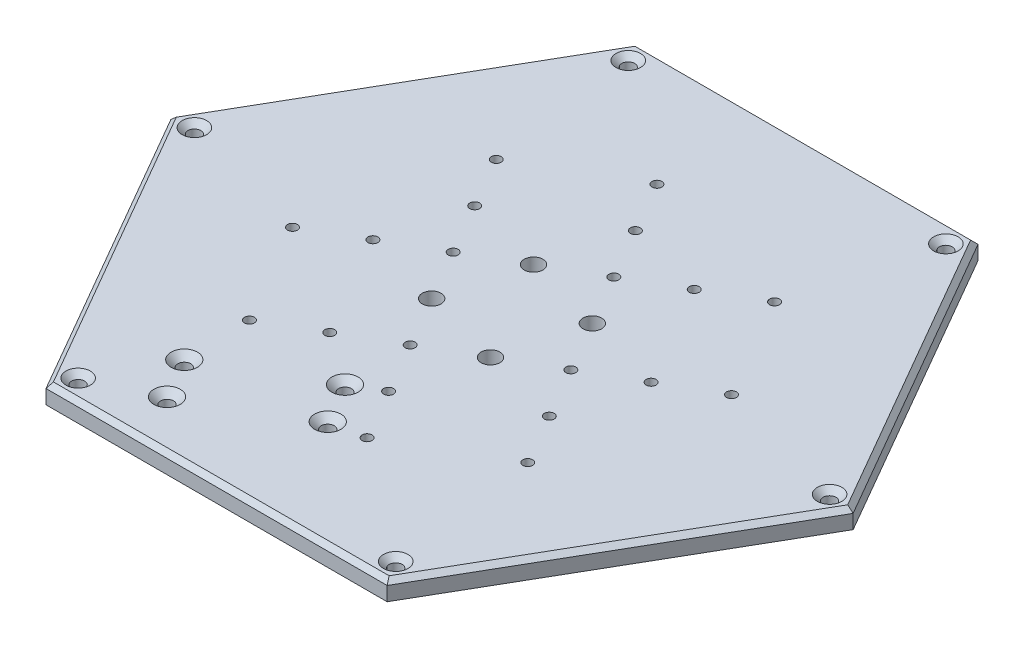
SolidWorks part; units mm, degrees
material "5052-H32"
ref_plane "Front Plane" through (0, 0, 0) normal (0, 0, 1) x (1, 0, 0)
ref_plane "Top Plane" through (0, 0, 0) normal (0, 1, 0) x (1, 0, 0)
ref_plane "Right Plane" through (0, 0, 0) normal (1, 0, 0) x (0, 0, -1)
sketch "Sketch1" plane through (0, 0, 0) normal (0, 1, 0) x (1, 0, 0)
  line L1 (72.5, 125.5737) -> (-72.5, 125.5737)
  line L2 (-72.5, 125.5737) -> (-145, 0)
  line L3 (-145, 0) -> (-72.5, -125.5737)
  line L4 (-72.5, -125.5737) -> (72.5, -125.5737)
  line L5 (72.5, -125.5737) -> (145, 0)
  line L6 (145, 0) -> (72.5, 125.5737)
  circle A0 centre (0, 0) radius 125.5737 construction
  dimension "D1" = 145
extrude "Boss-Extrude1" add sketch "Sketch1" along normal blind 8
sketch "Sketch10" plane through (0, 8, 0) normal (0, 1, 0) x (1, 0, 0)
  line L0 (145, 0) -> (0, 0) construction
  point P4 (135, 0)
  point P7 (67.5, -116.9134)
  point P8 (-67.5, -116.9134)
  point P9 (-135, 0)
  point P10 (-67.5, 116.9134)
  point P11 (67.5, 116.9134)
  point P12 (0, 0)
  dimension "D2" = 10
  dimension "D1" = 6
hole_wizard "CSK for M5 Flat Head Machine Screw2" positions "Sketch14" profile "Sketch13" countersink size "M5" standard "ANSI Metric"
sketch "Sketch14" plane through (0, 8, 0) normal (0, 1, 0) x (1, 0, 0)
  point P0 (-135, 0)
  point P3 (-67.5, -116.9134)
  point P6 (67.5, -116.9134)
  point P9 (135, 0)
  point P12 (67.5, 116.9134)
  point P15 (-67.5, 116.9134)
sketch "Sketch13" plane through (-135, 8, 0) normal (1, 0, 0) x (0, 0, 1)
  line L0 (0, 0) -> (0, 11.6524)
  line L1 (0, 11.6524) -> (2.75, 10)
  line L2 (2.75, 10) -> (2.75, 2.45)
  line L3 (2.75, 2.45) -> (5.2, 0)
  line L5 (5.2, 0) -> (0, 0)
  line L6 (-2.75, 2.45) -> (-5.2, 0) construction
  line L10 (0, 11.6524) -> (-2.75, 10) construction
  line L11 (0, -6.35) -> (0, 107.95) construction
  dimension "Hole Dia." = 5.5
  dimension "Hole Depth" = 10
  dimension "Near C'Sink Dia." = 10.4
  dimension "Near C'Sink Angle" = 90
  dimension "Drill Angle" = 118
sketch "Sketch19" plane through (0, 8, 0) normal (0, -1, 0) x (1, 0, 0)
  line L0 (1.5942, 79.9086) -> (-41.7071, 104.9086) construction
  line L1 (-41.7071, 104.9086) -> (-51.7071, 87.5881) construction
  line L2 (-51.7071, 87.5881) -> (-8.4058, 62.5881) construction
  line L3 (-8.4058, 62.5881) -> (1.5942, 79.9086) construction
  line L4 (-20.0564, 92.4086) -> (-25.0564, 83.7484) construction
  line L5 (-25.0564, 83.7484) -> (-3.4058, 71.2484) construction
  line L6 (-25.0564, 83.7484) -> (-78.75, 114.7484) construction
  line L7 (-145, 0) -> (-72.5, 125.5737) construction
  dimension "D1" = 50
  dimension "D2" = 20
  dimension "D3" = 62
  dimension "D4" = 12.5
hole_wizard "CSK for M5 SFHCS1" positions "Sketch21" profile "Sketch22" countersink size "M5" standard "ANSI Metric"
sketch "Sketch21" plane through (0, 8, 0) normal (0, 1, 0) x (1, 0, 0)
  point P0 (1.5942, -79.9086)
  point P3 (-8.4058, -62.5881)
  point P6 (-51.7071, -87.5881)
  point P9 (-41.7071, -104.9086)
sketch "Sketch22" plane through (1.5942, 8, 79.9086) normal (1, 0, 0) x (0, 0, 1)
  line L0 (0, 0) -> (0, 11.6524)
  line L1 (0, 11.6524) -> (2.75, 10)
  line L2 (2.75, 10) -> (2.75, 2.85)
  line L3 (2.75, 2.85) -> (5.6, 0)
  line L5 (5.6, 0) -> (0, 0)
  line L6 (-2.75, 2.85) -> (-5.6, 0) construction
  line L10 (0, 11.6524) -> (-2.75, 10) construction
  line L11 (0, -6.35) -> (0, 107.95) construction
  dimension "Hole Dia." = 5.5
  dimension "Hole Depth" = 10
  dimension "Near C'Sink Dia." = 11.2
  dimension "Near C'Sink Angle" = 90
  dimension "Drill Angle" = 118
sketch "Sketch15" plane through (0, 8, 0) normal (0, 1, 0) x (1, 0, 0)
  line L0 (0, 0) -> (108.75, 62.7868) construction
  line L2 (34.1506, -9.1506) -> (-9.1506, -34.1506) construction
  line L3 (46.6506, -30.8013) -> (3.3494, -55.8013) construction
  line L4 (59.1506, -52.4519) -> (15.8494, -77.4519) construction
  line L5 (9.1506, 34.1506) -> (34.1506, -9.1506) construction
  line L6 (-9.1506, -34.1506) -> (-34.1506, 9.1506) construction
  line L7 (-30.8013, -46.6506) -> (-55.8013, -3.3494) construction
  line L8 (30.8013, 46.6506) -> (55.8013, 3.3494) construction
  line L9 (-52.4519, -59.1506) -> (-77.4519, -15.8494) construction
  line L10 (52.4519, 59.1506) -> (77.4519, 15.8494) construction
  line L11 (-34.1506, 9.1506) -> (9.1506, 34.1506) construction
  line L12 (-46.6506, 30.8013) -> (-3.3494, 55.8013) construction
  line L13 (-59.1506, 52.4519) -> (-15.8494, 77.4519) construction
  line L14 (145, 0) -> (72.5, 125.5737) construction
  circle A1 centre (12.5, -21.6506) radius 4.7625 construction
  circle A2 centre (-21.6506, -12.5) radius 4.7625 construction
  circle A3 centre (-12.5, 21.6506) radius 4.7625 construction
  circle A29 centre (21.6506, 12.5) radius 4.7625 construction
  point P4 (108.75, 62.7868)
  point P23 (43.3013, 25)
  point P26 (64.9519, 37.5)
  point P70 (0, 0)
  point P71 (0, 0)
  point P81 (0, 0)
  dimension "D3" = 25
  dimension "D7" = 9.525
  dimension "D4" = 25
  dimension "D1" = 50
  dimension "D5" = 25
  dimension "D6" = 4
hole_wizard "M5x0.8 Tapped Hole1" positions "Sketch24" profile "Sketch23" tap size "M5x0.8" standard "ANSI Metric" end condition through all
sketch "Sketch24" plane through (0, 8, 0) normal (0, 1, 0) x (1, 0, 0)
  point P0 (59.1506, -52.4519)
  point P3 (15.8494, -77.4519)
  point P6 (3.3494, -55.8013)
  point P9 (46.6506, -30.8013)
  point P12 (34.1506, -9.1506)
  point P15 (9.1506, 34.1506)
  point P18 (-34.1506, 9.1506)
  point P21 (-9.1506, -34.1506)
  point P24 (-30.8013, -46.6506)
  point P27 (-52.4519, -59.1506)
  point P30 (-77.4519, -15.8494)
  point P33 (-55.8013, -3.3494)
  point P36 (-46.6506, 30.8013)
  point P39 (-59.1506, 52.4519)
  point P42 (-15.8494, 77.4519)
  point P45 (-3.3494, 55.8013)
  point P48 (30.8013, 46.6506)
  point P51 (55.8013, 3.3494)
  point P54 (77.4519, 15.8494)
  point P57 (52.4519, 59.1506)
sketch "Sketch23" plane through (59.1506, 8, 52.4519) normal (1, 0, 0) x (0, 0, 1)
  line L0 (0, 0) -> (0, 8)
  line L1 (0, 8) -> (2.1, 8)
  line L2 (2.1, 8) -> (2.1, 0)
  line L5 (2.1, 0) -> (0, 0)
  line L11 (0, -6.35) -> (0, 107.95) construction
  dimension "Thru Tap Drill Dia." = 4.2
  dimension "Thru Tap Drill Depth" = 8
cosmetic thread "Hole Thread1" parameters "D2"=5
cosmetic thread "Hole Thread2" parameters "D2"=5
cosmetic thread "Hole Thread3" parameters "D2"=5
cosmetic thread "Hole Thread4" parameters "D2"=5
cosmetic thread "Hole Thread5" parameters "D2"=5
cosmetic thread "Hole Thread6" parameters "D2"=5
cosmetic thread "Hole Thread7" parameters "D2"=5
cosmetic thread "Hole Thread8" parameters "D2"=5
cosmetic thread "Hole Thread9" parameters "D2"=5
cosmetic thread "Hole Thread10" parameters "D2"=5
cosmetic thread "Hole Thread11" parameters "D2"=5
cosmetic thread "Hole Thread12" parameters "D2"=5
cosmetic thread "Hole Thread13" parameters "D2"=5
cosmetic thread "Hole Thread14" parameters "D2"=5
cosmetic thread "Hole Thread15" parameters "D2"=5
cosmetic thread "Hole Thread16" parameters "D2"=5
cosmetic thread "Hole Thread17" parameters "D2"=5
cosmetic thread "Hole Thread18" parameters "D2"=5
cosmetic thread "Hole Thread19" parameters "D2"=5
cosmetic thread "Hole Thread20" parameters "D2"=5
hole_wizard "3/8-16 Tapped Hole3" positions "Sketch29" profile "Sketch28" tap size "3/8-16" standard "ANSI Inch" end condition through all
sketch "Sketch29" plane through (0, 8, 0) normal (0, 1, 0) x (1, 0, 0)
  point P0 (12.5, -21.6506)
  point P3 (-21.6506, -12.5)
  point P6 (-12.5, 21.6506)
  point P9 (21.6506, 12.5)
sketch "Sketch28" plane through (12.5, 8, 21.6506) normal (1, 0, 0) x (0, 0, 1)
  line L0 (0, 0) -> (0, 8)
  line L1 (0, 8) -> (3.9687, 8)
  line L2 (3.9687, 8) -> (3.9687, 0)
  line L5 (3.9687, 0) -> (0, 0)
  line L11 (0, -6.35) -> (0, 107.95) construction
  dimension "Thru Tap Drill Dia." = 7.9375
  dimension "Thru Tap Drill Depth" = 8
cosmetic thread "Hole Thread25" parameters "D2"=9.525
cosmetic thread "Hole Thread26" parameters "D2"=9.525
cosmetic thread "Hole Thread27" parameters "D2"=9.525
cosmetic thread "Hole Thread28" parameters "D2"=9.525
chamfer "Chamfer4" distance 2 angle 45 6 edges at (0, 8, 125.5737) (108.75, 8, 62.7868) (108.75, 8, -62.7868) (0, 8, -125.5737) (-108.75, 8, -62.7868) (-108.75, 8, 62.7868)
